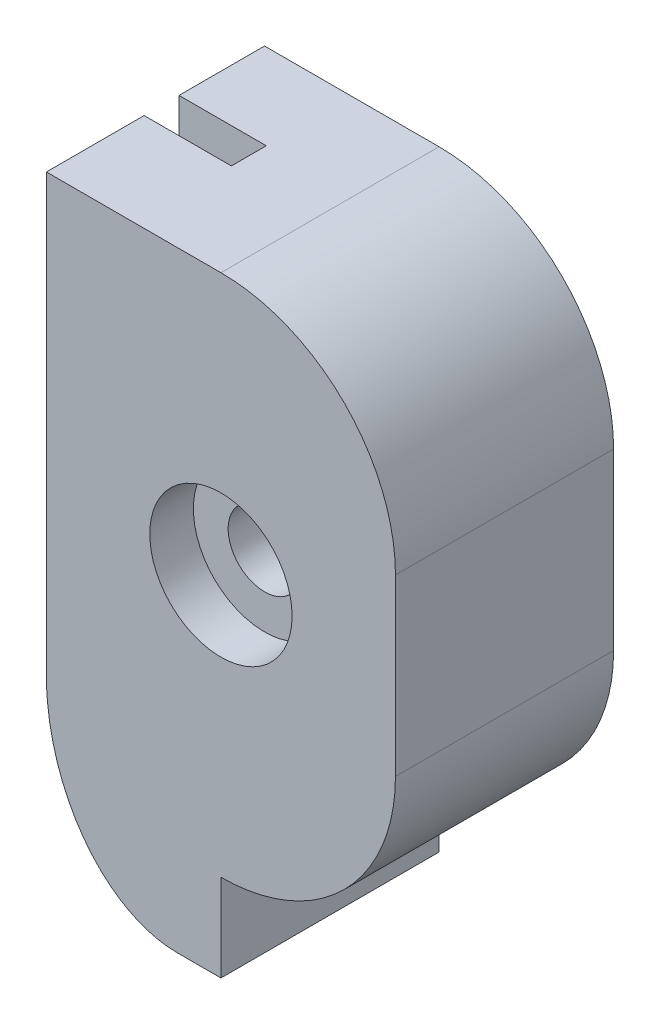
SolidWorks part; units mm, degrees
ref_plane "Ebene vorne" through (0, 0, 0) normal (0, 0, 1) x (1, 0, 0)
ref_plane "Ebene oben" through (0, 0, 0) normal (0, 1, 0) x (1, 0, 0)
ref_plane "Ebene rechts" through (0, 0, 0) normal (1, 0, 0) x (0, 0, -1)
sketch "Sketch1" plane through (0, 0, 0) normal (0, 0, 1) x (1, 0, 0)
  line L0 (-20, 0) -> (20, 0) construction
  line L1 (-20, 30) -> (20, 30)
  line L2 (-20, 30) -> (-20, -30)
  line L3 (-20, -30) -> (20, -30)
  line L4 (20, 30) -> (20, -30)
  line L5 (0, -30) -> (0, 30) construction
  point P9 (0, 0)
  dimension "D1" = 40
  dimension "D2" = 60
extrude "Boss-Extrude1" add sketch "Sketch1" along normal mid plane 25 contours L1 L4 L3 L2
sketch "Sketch3" plane through (0, 0, 0) normal (1, 0, 0) x (0, 0, -1)
  line L0 (-12.5, -8.1575) -> (-7.5, -8.1575)
  line L1 (-7.5, -8.1575) -> (-7.5, -4.1698)
  line L2 (-7.5, -4.1698) -> (7.5, -4.1698)
  line L3 (7.5, -4.1698) -> (7.5, -8.1575)
  line L4 (7.5, -8.1575) -> (12.5, -8.1575)
  line L5 (-12.5, 30) -> (-12.5, -30) construction
  line L6 (-19.1694, 0) -> (24.4545, 0) construction
  line L7 (-12.5, -8.1575) -> (-12.5, 0)
  line L8 (12.5, -8.1575) -> (12.5, 0)
  line L9 (-12.5, 0) -> (12.5, 0)
  dimension "D1" = 5
  dimension "D2" = 5
  dimension "D3" = 25
revolve "Cut-Revolve1" cut sketch "Sketch3" angle 360 about L6
sketch "Sketch4" plane through (-20, 0, 0) normal (-1, 0, 0) x (0, 0, 1)
  line L0 (12.5, 30) -> (-12.5, 30) construction
  line L1 (-2.6959, 30) -> (1.3041, 30)
  line L2 (-2.6959, 30) -> (-2.6959, -30)
  line L3 (-2.6959, -30) -> (1.3041, -30)
  line L4 (1.3041, 30) -> (1.3041, -30)
  line L5 (12.5, -30) -> (-12.5, -30) construction
  line L6 (-0.6959, 30) -> (-0.6959, -30) construction
  dimension "D1" = 4
extrude "Cut-Extrude1" cut sketch "Sketch4" against normal blind 10
sketch "Sketch5" plane through (0, 0, -12.5) normal (0, 0, 1) x (1, 0, 0)
  line L0 (0, -5.5) -> (-20, 1.7794)
  line L2 (-20, 30) -> (-20, -30) construction
  line L3 (0, -4.0953) -> (-20, 3.1841)
  line L5 (0, -5.5) -> (-20, -5.5) construction
  line L6 (0, -13.75) -> (0, 13.75) construction
  line L7 (-20, 3.1841) -> (-20, 1.7794)
  line L8 (0, -4.0953) -> (0, -5.5)
  circle A0 centre (0, 0) radius 5.5 construction
  point P12 (-10, -1.8603)
  dimension "D1" = 11
  dimension "D2" = 1.32
  dimension "D3" = 20
extrude "Cut-Extrude2" cut sketch "Sketch5" along normal blind 4
fillet "Fillet1" radius 20 2 edges at (20, -30, 0) (20, 30, 0)
sketch "Sketch6" plane through (0, -30, 0) normal (0, 1, 0) x (1, 0, 0)
  line L0 (-20, 12.5) -> (0, 12.5) construction
  line L1 (-20, -12.5) -> (0, -12.5)
  line L2 (-20, -12.5) -> (-20, 12.5)
  line L3 (-20, 12.5) -> (0, 12.5)
  line L4 (0, -12.5) -> (0, 12.5)
extrude "Boss-Extrude2" add sketch "Sketch6" against normal blind 10 contours L3 L4 L1 L2
fillet "Fillet2" radius 20 1 edges at (-20, -40, 0) second distance 15 first distance on face at (-20, -0.8394, -3.732)
